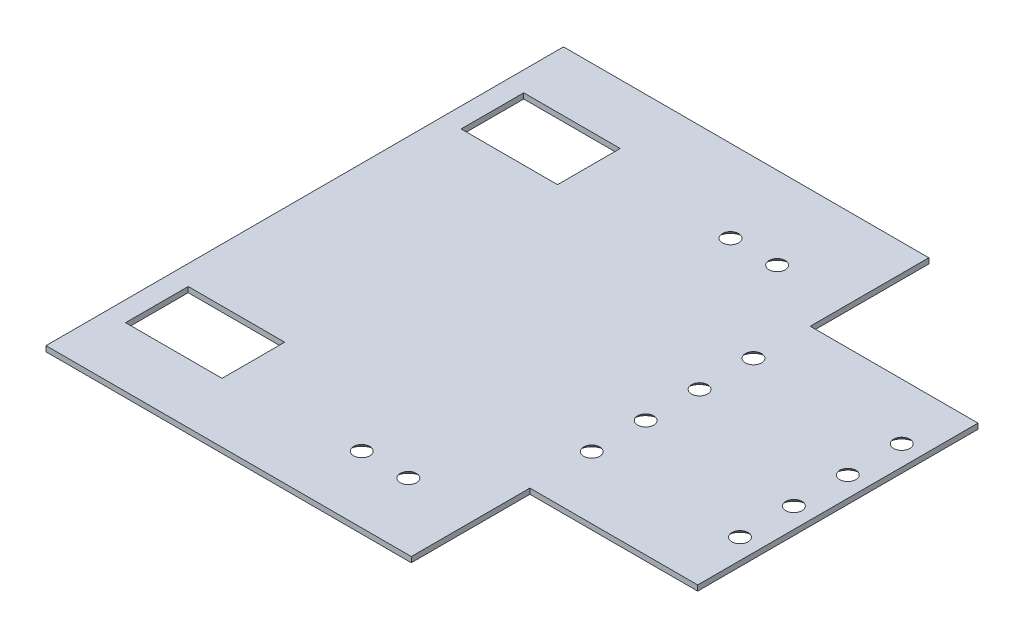
SolidWorks part; units mm, degrees
ref_plane "Спереди" through (0, 0, 0) normal (0, 0, 1) x (1, 0, 0)
ref_plane "Сверху" through (0, 0, 0) normal (0, 1, 0) x (1, 0, 0)
ref_plane "Справа" through (0, 0, 0) normal (1, 0, 0) x (0, 0, -1)
sketch "Эскиз1" plane through (0, 0, 0) normal (0, 1, 0) x (1, 0, 0)
  line L5 (49.9338, 26) -> (18.8099, 26)
  line L6 (49.9338, 26) -> (49.9338, -26)
  line L7 (49.9338, -26) -> (18.8099, -26)
  line L8 (-48.9591, 48) -> (15, 48)
  line L9 (-48.9591, 48) -> (-48.9591, -48)
  line L10 (-50, 0) -> (49.9338, 0) construction
  line L11 (-48.9591, -48) -> (15, -48)
  line L12 (-45.2656, -36.9305) -> (-45.2656, -25.3095)
  line L13 (-45.2656, 36.9305) -> (-27.3726, 36.9305)
  line L14 (-45.2656, 36.9305) -> (-45.2656, 25.3095)
  line L15 (-45.2656, 25.3095) -> (-27.3726, 25.3095)
  line L16 (-27.3726, 36.9305) -> (-27.3726, 25.3095)
  line L21 (-45.2656, -25.3095) -> (-27.3726, -25.3095)
  line L22 (-27.3726, -36.9305) -> (-27.3726, -25.3095)
  line L23 (-45.2656, -36.9305) -> (-27.3726, -36.9305)
  line L24 (-15.0662, -48) -> (20.6445, -48) construction
  line L27 (15, -48) -> (18.8099, -48)
  line L28 (18.8099, -26) -> (18.8099, -48)
  line L29 (15, 48) -> (18.8099, 48)
  line L30 (18.8099, 26) -> (18.8099, 48)
  line L31 (19.8099, 48) -> (19.8099, 26) construction
  line L32 (18.0113, 27.0025) -> (47.8563, 27.0025) construction
  dimension "D1" = 1
  dimension "D2" = 1.0025
extrude "Бобышка-Вытянуть1" add sketch "Эскиз1" along normal blind 1
sketch "Эскиз2" plane through (0, 1, 0) normal (0, 1, 0) x (1, 0, 0)
  circle A0 centre (46.1838, -14.4) radius 1.5
  circle A1 centre (18.6838, -14.4) radius 1.5
  circle A2 centre (18.6838, -4.4) radius 1.5
  circle A3 centre (46.1838, -4.4) radius 1.5
  circle A4 centre (18.6838, 5.6) radius 1.5
  circle A5 centre (46.1838, 5.6) radius 1.5
  circle A6 centre (18.6838, 15.6) radius 1.5
  circle A7 centre (46.1838, 15.6) radius 1.5
  dimension "D1" = 4
extrude "Вырез-Вытянуть1" cut sketch "Эскиз2" against normal blind 10
chamfer "Фаска1" distance 1 angle 45 8 edges at (18.6838, 0, -17.1) (18.6838, 0, -7.1) (18.6838, 0, 2.9) (18.6838, 0, 12.9) (46.1838, 0, -17.1) (46.1838, 0, -7.1) (46.1838, 0, 2.9) (46.1838, 0, 12.9)
sketch "Эскиз3" plane through (0, 1, 0) normal (0, 1, 0) x (1, 0, 0)
  circle A0 centre (5.9236, 32.747) radius 1.5
  circle A1 centre (-2.7264, 32.747) radius 1.5
  circle A2 centre (-2.7264, -35.6602) radius 1.5
  circle A3 centre (5.9236, -35.6602) radius 1.5
extrude "Вырез-Вытянуть2" cut sketch "Эскиз3" against normal blind 10
chamfer "Фаска2" distance 1 angle 45 4 edges at (-2.7264, 0, 34.1602) (5.9236, 0, 34.1602) (-2.7264, 0, -34.247) (5.9236, 0, -34.247)
